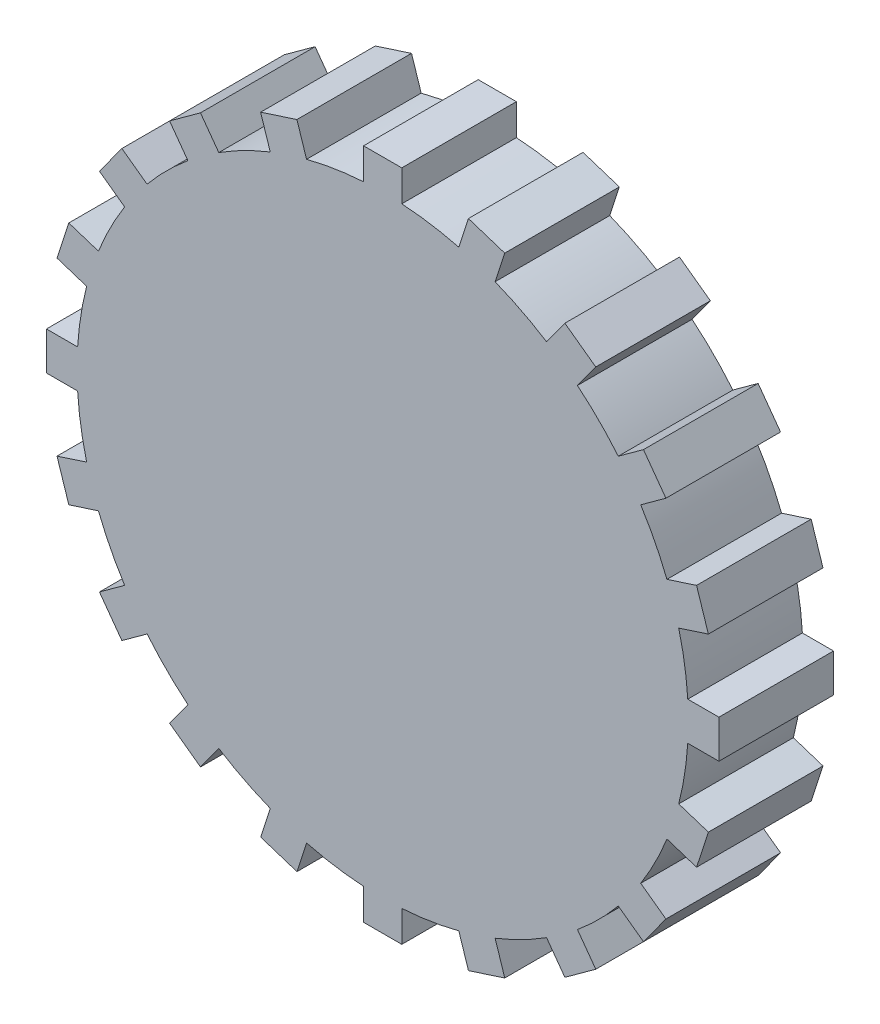
SolidWorks part; units mm, degrees
ref_plane "前视基准面" through (0, 0, 0) normal (0, 0, 1) x (1, 0, 0)
ref_plane "上视基准面" through (0, 0, 0) normal (0, 1, 0) x (1, 0, 0)
ref_plane "右视基准面" through (0, 0, 0) normal (1, 0, 0) x (0, 0, -1)
other "Configuration Table"
sketch "草图1" plane through (0, 0, 0) normal (0, 0, 1) x (1, 0, 0)
  circle A0 centre (0, 0) radius 40
extrude "凸台-拉伸1" add sketch "草图1" along normal blind 15
sketch "草图2" plane through (0, 0, 0) normal (0, 0, 1) x (1, 0, 0)
  line L1 (39.9221, -2.4951) -> (44, -2.4951)
  line L2 (39.9221, -2.4951) -> (39.9221, 2.5)
  line L3 (39.9221, 2.5) -> (44, 2.5)
  line L4 (44, -2.4951) -> (44, 2.5)
  circle A0 centre (0, 0) radius 40 construction
extrude "凸台-拉伸2" add sketch "草图2" along normal blind 15
ref_axis "基准轴1" through (0, 0, 15) along (0, 0, -1)
pattern_circular "阵列(圆周)1" count 20 over 360 about axis through (0, 0, 15) along (0, 0, -1) of "凸台-拉伸2"
